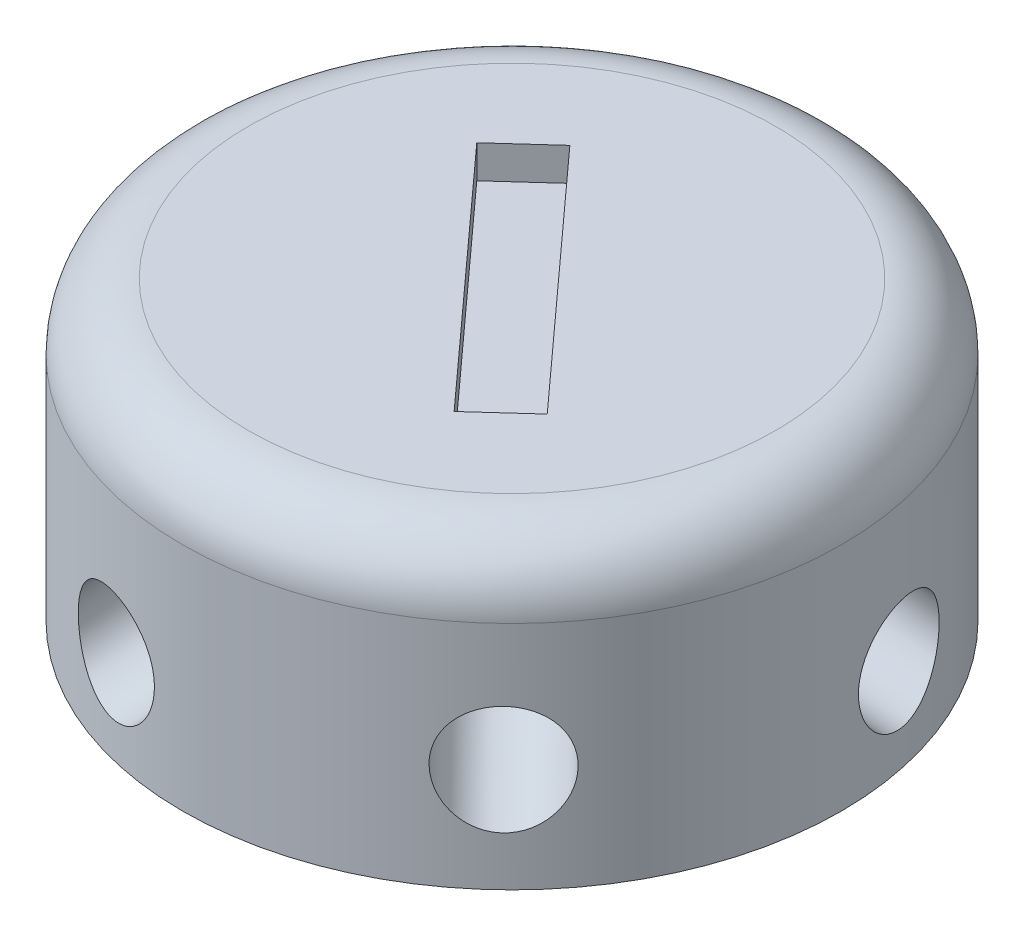
SolidWorks part; units mm, degrees
ref_plane "Front Plane" through (0, 0, 0) normal (0, 0, 1) x (1, 0, 0)
ref_plane "Top Plane" through (0, 0, 0) normal (0, 1, 0) x (1, 0, 0)
ref_plane "Right Plane" through (0, 0, 0) normal (1, 0, 0) x (0, 0, -1)
sketch "Sketch1" plane through (0, 0, 0) normal (0, 1, 0) x (1, 0, 0)
  circle A0 centre (0, 0) radius 10
  dimension "D1" = 20
extrude "base" add sketch "Sketch1" along normal blind 3 and the other way blind 6
ref_axis "6hubaxis" through (0, 5.5, 0) along (0, -1, 0)
ref_plane "Plane1" through (2.6705, -1.0931, 2.7701) normal (-0.6676, 0.2733, -0.6925) x (-0.6559, 0.2243, 0.7208)
sketch "Sketch2" plane through (2.6705, -1.0931, 2.7701) normal (-0.6676, 0.2733, -0.6925) x (-0.6559, 0.2243, 0.7208)
  circle A0 centre (0, 0) radius 1.5 construction
  circle A1 centre (0, 0) radius 1.5 construction
  circle A2 centre (0, 0) radius 1.6
  dimension "D1" = 3.2
extrude "hole1" cut sketch "Sketch2" against normal through all
pattern_circular "hole1mirror" count 2 over 360 about axis through (0, 5.5, 0) along (0, -1, 0) of "hole1"
ref_plane "Plane2" through (-0.9417, -1.2361, 3.6858) normal (0.2354, 0.309, -0.9215) x (-0.9719, 0.0738, -0.2235)
sketch "Sketch3" plane through (-0.9417, -1.2361, 3.6858) normal (0.2354, 0.309, -0.9215) x (-0.9719, 0.0738, -0.2235)
  circle A0 centre (0, 0) radius 1.5 construction
  circle A1 centre (0, 0) radius 1.5 construction
  circle A2 centre (0, 0) radius 1.6
  dimension "D1" = 3.2
extrude "hole2" cut sketch "Sketch3" against normal through all
pattern_circular "hole2mirror" count 2 over 360 about axis through (0, 5.5, 0) along (0, -1, 0) of "hole2"
ref_plane "Plane3" through (-3.7178, -1.2361, 0.8061) normal (0.9295, 0.309, -0.2015) x (-0.1912, -0.0636, -0.9795)
sketch "Sketch4" plane through (-3.7178, -1.2361, 0.8061) normal (0.9295, 0.309, -0.2015) x (-0.1912, -0.0636, -0.9795)
  circle A0 centre (0, 0) radius 1.5 construction
  circle A1 centre (0, 0) radius 1.5 construction
  circle A2 centre (0, 0) radius 1.6
  dimension "D1" = 3.2
extrude "hole3" cut sketch "Sketch4" against normal through all
pattern_circular "hole3mirror" count 2 over 360 about axis through (0, 5.5, 0) along (0, -1, 0) of "hole3"
fillet "Fillet1" radius 2 1 edges at (0, 3, 10)
sketch "Sketch6" plane through (0, 3, 0) normal (0, 1, 0) x (1, 0, 0)
  line L0 (5.3752, -5.9251) -> (-5.3752, 5.9251) construction
  line L1 (-4.1001, 3.0313) -> (-2.6189, 4.3751)
  line L2 (-2.6189, 4.3751) -> (4.1001, -3.0313)
  line L3 (4.1001, -3.0313) -> (2.6189, -4.3751)
  line L4 (2.6189, -4.3751) -> (-4.1001, 3.0313)
  line L5 (-0.7406, -0.6719) -> (0.7406, 0.6719) construction
  circle A0 centre (0, 0) radius 8 construction
  point P6 (0.7406, 0.6719)
  point P10 (3.3595, -3.7032)
  dimension "D1" = 2
  dimension "D2" = 10
extrude "Cut-Extrude1" cut sketch "Sketch6" against normal blind 1
